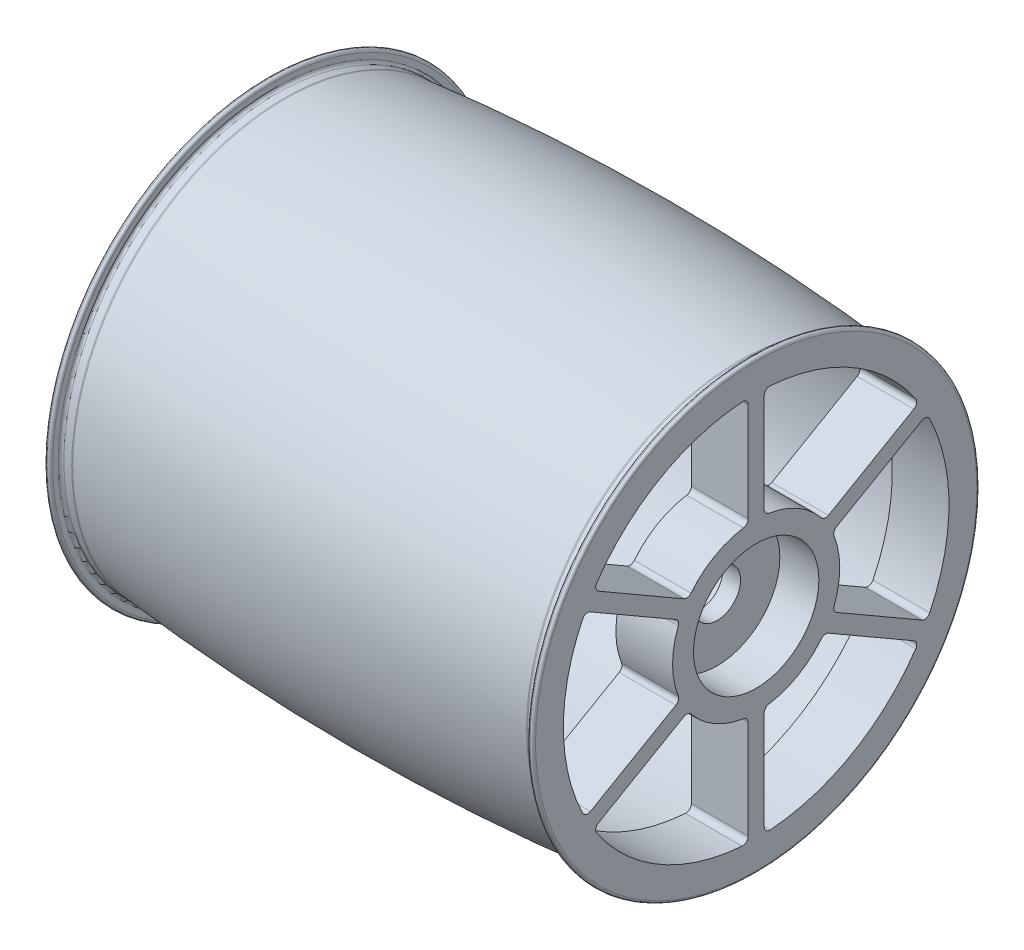
SolidWorks part; units mm, degrees
ref_plane "Front Plane" through (0, 0, 0) normal (0, 0, 1) x (1, 0, 0)
ref_plane "Top Plane" through (0, 0, 0) normal (0, 1, 0) x (1, 0, 0)
ref_plane "Right Plane" through (0, 0, 0) normal (1, 0, 0) x (0, 0, -1)
sketch "Sketch1" plane through (0, 0, 0) normal (0, 0, 1) x (1, 0, 0)
  line L0 (-40.815, 0) -> (40.815, 0) construction
  line L1 (-40.815, 0) -> (-40.815, 38.1) construction
  line L2 (40.815, 0) -> (40.815, 38.1) construction
  line L3 (0, 0) -> (0, 40.1) construction
  line L4 (-40.815, 38.1) -> (-42.815, 38.1)
  line L5 (40.815, 38.1) -> (42.815, 38.1)
  line L9 (-42.815, 38.1) -> (-42.815, 40.1)
  line L10 (-42.815, 40.1) -> (-43.815, 40.1)
  line L11 (-43.815, 40.1) -> (-43.815, 0)
  line L12 (-43.815, 0) -> (-33.64, 0)
  line L14 (42.815, 38.1) -> (42.815, 40.1)
  line L15 (42.815, 40.1) -> (43.815, 40.1)
  line L16 (43.815, 40.1) -> (43.815, 0)
  line L17 (43.815, 0) -> (33.64, 0)
  line L19 (-33.64, 0) -> (-33.64, 37.7391)
  line L20 (33.64, 0) -> (33.64, 37.7391)
  arc A0 (-40.815, 38.1) -> (40.815, 38.1) centre (0, -377.3661) cw
  arc A1 (-33.64, 37.7391) -> (33.64, 37.7391) centre (0, -377.3661) cw
  dimension "D3" = 1
  dimension "D1" = 38.1
  dimension "D4" = 2
  dimension "D8" = 1
  dimension "D9" = 40.1
  dimension "D10" = 10.175
  dimension "D2" = 87.63
revolve "Revolve2" add sketch "Sketch1" angle 360 about L0
fillet "Fillet2" radius 2 4 edges at (40.815, 0, 38.1) (-40.815, 0, 38.1) (33.64, 0, 37.7391) (-33.64, 0, 37.7391)
fillet "Fillet1" radius 0.5 6 edges at (43.815, 0, 40.1) (42.815, 0, 40.1) (42.815, 0, 38.1) (-42.815, 0, 38.1) (-42.815, 0, 40.1) (-43.815, 0, 40.1)
sketch "Sketch2" plane through (-43.815, 0, 0) normal (-1, 0, 0) x (0, 0, 1)
  line L0 (0, 0) -> (13.6518, 0) construction
  line L1 (14.4156, 6.6562) -> (29.7431, 15.5055)
  line L2 (13.6518, 6.2152) -> (13.6518, -6.2152) construction
  line L3 (14.4156, -6.6562) -> (29.7431, -15.5055)
  line L4 (30.6601, 16.0349) -> (30.6601, -16.0349) construction
  line L5 (2.8868, 0) -> (13.6518, 6.2152) construction
  line L6 (2.8868, 0) -> (1.4434, 2.5) construction
  line L7 (1.4434, 2.5) -> (-1.4434, 2.5) construction
  line L8 (-1.4434, 2.5) -> (-2.8868, 0) construction
  line L9 (-2.8868, 0) -> (-1.4434, -2.5) construction
  line L10 (-1.4434, -2.5) -> (1.4434, -2.5) construction
  line L11 (1.4434, -2.5) -> (2.8868, 0) construction
  line L12 (13.6518, 0) -> (30.6601, 0) construction
  line L13 (13.6518, -6.2152) -> (2.8868, 0) construction
  line L14 (12.9722, -9.1562) -> (28.2997, -18.0055)
  line L15 (1.4434, -15.8123) -> (1.4434, -33.511)
  line L16 (-1.4434, -15.8123) -> (-1.4434, -33.511)
  line L17 (-12.9722, -9.1562) -> (-28.2997, -18.0055)
  line L18 (-14.4156, -6.6562) -> (-29.7431, -15.5055)
  line L19 (-14.4156, 6.6562) -> (-29.7431, 15.5055)
  line L20 (-12.9722, 9.1562) -> (-28.2997, 18.0055)
  line L21 (-1.4434, 15.8123) -> (-1.4434, 33.511)
  line L22 (1.4434, 15.8123) -> (1.4434, 33.511)
  line L23 (12.9722, 9.1562) -> (28.2997, 18.0055)
  arc A0 (31.1432, 15.0752) -> (31.1432, -15.0752) centre (0, 0) cw
  circle A1 centre (0, 0) radius 39.6 construction
  circle A2 centre (0, 0) radius 2.5 construction
  arc A3 (13.9833, 5.4283) -> (13.9833, -5.4283) centre (0, 0) cw
  arc A4 (13.9833, -5.4283) -> (14.4156, -6.6562) centre (14.9156, -5.7901) ccw
  arc A5 (14.4156, 6.6562) -> (13.9833, 5.4283) centre (14.9156, 5.7901) ccw
  arc A6 (29.7431, -15.5055) -> (31.1432, -15.0752) centre (30.2431, -14.6395) ccw
  arc A7 (31.1432, 15.0752) -> (29.7431, 15.5055) centre (30.2431, 14.6395) ccw
  arc A8 (28.6271, -19.4332) -> (28.2997, -18.0055) centre (27.7997, -18.8715) ccw
  arc A9 (28.6271, -19.4332) -> (2.5161, -34.5084) centre (0, 0) cw
  arc A10 (1.4434, -33.511) -> (2.5161, -34.5084) centre (2.4434, -33.511) ccw
  arc A11 (2.2907, -14.8241) -> (1.4434, -15.8123) centre (2.4434, -15.8123) ccw
  arc A12 (11.6927, -9.3958) -> (2.2907, -14.8241) centre (0, 0) cw
  arc A13 (12.9722, -9.1562) -> (11.6927, -9.3958) centre (12.4722, -10.0222) ccw
  arc A14 (-2.5161, -34.5084) -> (-1.4434, -33.511) centre (-2.4434, -33.511) ccw
  arc A15 (-2.5161, -34.5084) -> (-28.6271, -19.4332) centre (0, 0) cw
  arc A16 (-28.2997, -18.0055) -> (-28.6271, -19.4332) centre (-27.7997, -18.8715) ccw
  arc A17 (-11.6927, -9.3958) -> (-12.9722, -9.1562) centre (-12.4722, -10.0222) ccw
  arc A18 (-2.2907, -14.8241) -> (-11.6927, -9.3958) centre (0, 0) cw
  arc A19 (-1.4434, -15.8123) -> (-2.2907, -14.8241) centre (-2.4434, -15.8123) ccw
  arc A20 (-31.1432, -15.0752) -> (-29.7431, -15.5055) centre (-30.2431, -14.6395) ccw
  arc A21 (-31.1432, -15.0752) -> (-31.1432, 15.0752) centre (0, 0) cw
  arc A22 (-29.7431, 15.5055) -> (-31.1432, 15.0752) centre (-30.2431, 14.6395) ccw
  arc A23 (-13.9833, 5.4283) -> (-14.4156, 6.6562) centre (-14.9156, 5.7901) ccw
  arc A24 (-13.9833, -5.4283) -> (-13.9833, 5.4283) centre (0, 0) cw
  arc A25 (-14.4156, -6.6562) -> (-13.9833, -5.4283) centre (-14.9156, -5.7901) ccw
  arc A26 (-28.6271, 19.4332) -> (-28.2997, 18.0055) centre (-27.7997, 18.8715) ccw
  arc A27 (-28.6271, 19.4332) -> (-2.5161, 34.5084) centre (0, 0) cw
  arc A28 (-1.4434, 33.511) -> (-2.5161, 34.5084) centre (-2.4434, 33.511) ccw
  arc A29 (-2.2907, 14.8241) -> (-1.4434, 15.8123) centre (-2.4434, 15.8123) ccw
  arc A30 (-11.6927, 9.3958) -> (-2.2907, 14.8241) centre (0, 0) cw
  arc A31 (-12.9722, 9.1562) -> (-11.6927, 9.3958) centre (-12.4722, 10.0222) ccw
  arc A32 (2.5161, 34.5084) -> (1.4434, 33.511) centre (2.4434, 33.511) ccw
  arc A33 (2.5161, 34.5084) -> (28.6271, 19.4332) centre (0, 0) cw
  arc A34 (28.2997, 18.0055) -> (28.6271, 19.4332) centre (27.7997, 18.8715) ccw
  arc A35 (11.6927, 9.3958) -> (12.9722, 9.1562) centre (12.4722, 10.0222) ccw
  arc A36 (2.2907, 14.8241) -> (11.6927, 9.3958) centre (0, 0) cw
  arc A37 (1.4434, 15.8123) -> (2.2907, 14.8241) centre (2.4434, 15.8123) ccw
  point P92 (0, 0)
  dimension "D5" = 5
  dimension "D2" = 15
  dimension "D3" = 1
  dimension "D4" = 5
  dimension "D1" = 30
  dimension "D6" = 6
extrude "Cut-Extrude2" cut sketch "Sketch2" against normal through all
sketch "Sketch7" plane through (43.815, 0, 0) normal (1, 0, 0) x (0, 0, -1)
  circle A0 centre (0, 0) radius 4.2
  dimension "D1" = 8.4
extrude "Cut-Extrude5" cut sketch "Sketch7" against normal through all both and the other way through all
sketch "Sketch8" plane through (43.815, 0, 0) normal (1, 0, 0) x (0, 0, -1)
  circle A0 centre (0, 0) radius 11.25
  dimension "D1" = 22.5
extrude "Cut-Extrude6" cut sketch "Sketch8" against normal blind 7
ref_plane "Plane1" through (0, 0, 0) normal (1, 0, 0) x (0, -1, 0)
mirror "Mirror1" about plane through (0, 0, 0) normal (1, 0, 0) of "Cut-Extrude6"
equation "\"SpokeWidth\"= 5"
equation "\"D5@Sketch2\" = \"SpokeWidth\""
equation "\"HubDiameter\"= 30"
equation "\"D2@Sketch2\"=\"HubDiameter\"/2"
equation "\"PulleyDiameter\"= 3in"
equation "\"D1@Sketch1\"=\"PulleyDiameter\"/2"
equation "\"D9@Sketch1\"=(\"PulleyDiameter\"/2) + 2"
equation "\"PulleyWidth\" = 3.45in"
equation "\"RimWidth\"= 5"
equation "\"D4@Sketch2\"=\"RimWidth\""
equation "\"D2@Sketch1\"=\"PulleyWidth\""
